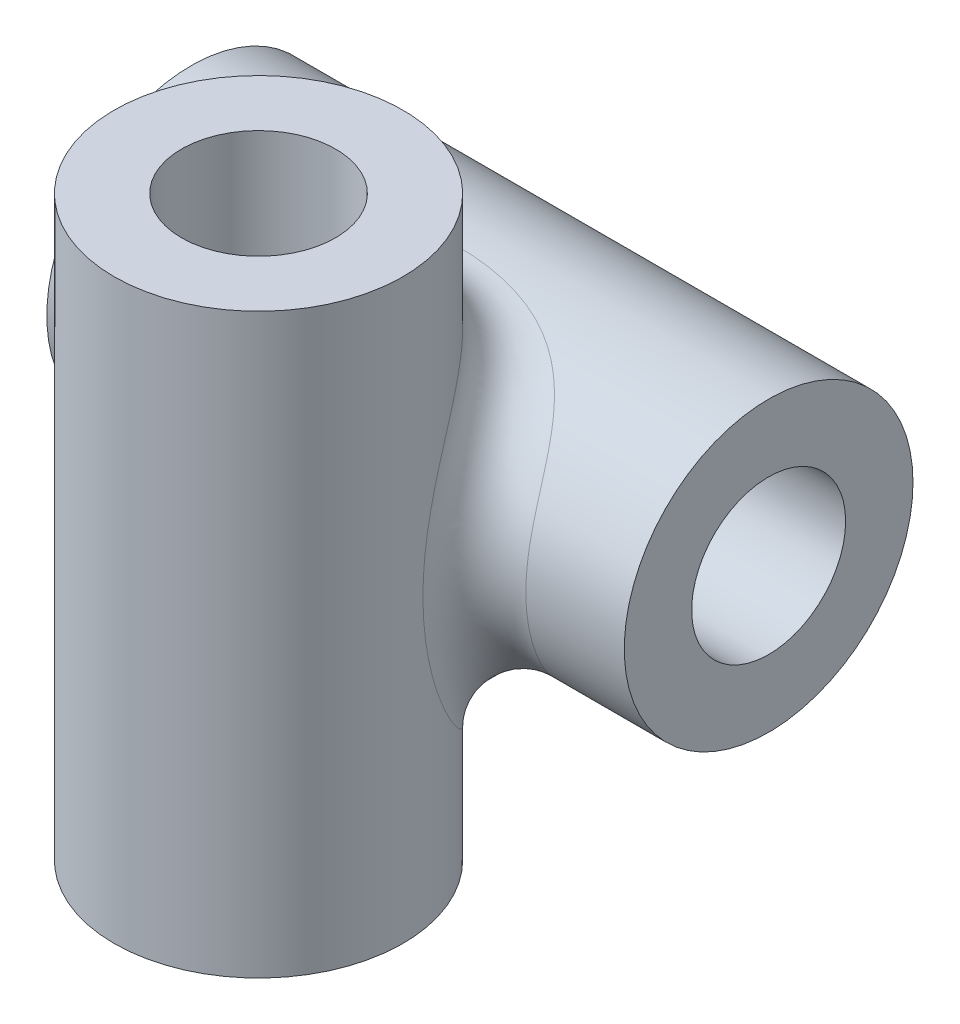
SolidWorks part; units mm, degrees
ref_plane "Front Plane" through (0, 0, 0) normal (0, 0, 1) x (1, 0, 0)
ref_plane "Top Plane" through (0, 0, 0) normal (0, 1, 0) x (1, 0, 0)
ref_plane "Right Plane" through (0, 0, 0) normal (1, 0, 0) x (0, 0, -1)
sketch "Sketch2" plane through (0, 0, 0) normal (0, 1, 0) x (1, 0, 0)
  circle A0 centre (0, 0) radius 8
  circle A1 centre (0, 0) radius 15
  dimension "D1" = 16
  dimension "D2" = 30
extrude "Boss-Extrude1" add sketch "Sketch2" along normal mid plane 60
sketch "Sketch3" plane through (0, 0, 0) normal (1, 0, 0) x (0, 0, -1)
  circle A0 centre (23, 0) radius 8
  circle A1 centre (23, 0) radius 15
  dimension "D2" = 16
  dimension "D3" = 30
  dimension "D1" = 23
extrude "Boss-Extrude2" add sketch "Sketch3" along normal mid plane 60
fillet "Fillet1" radius 5 1 edges at (-3.3823, -12.4366, -14.6137)
